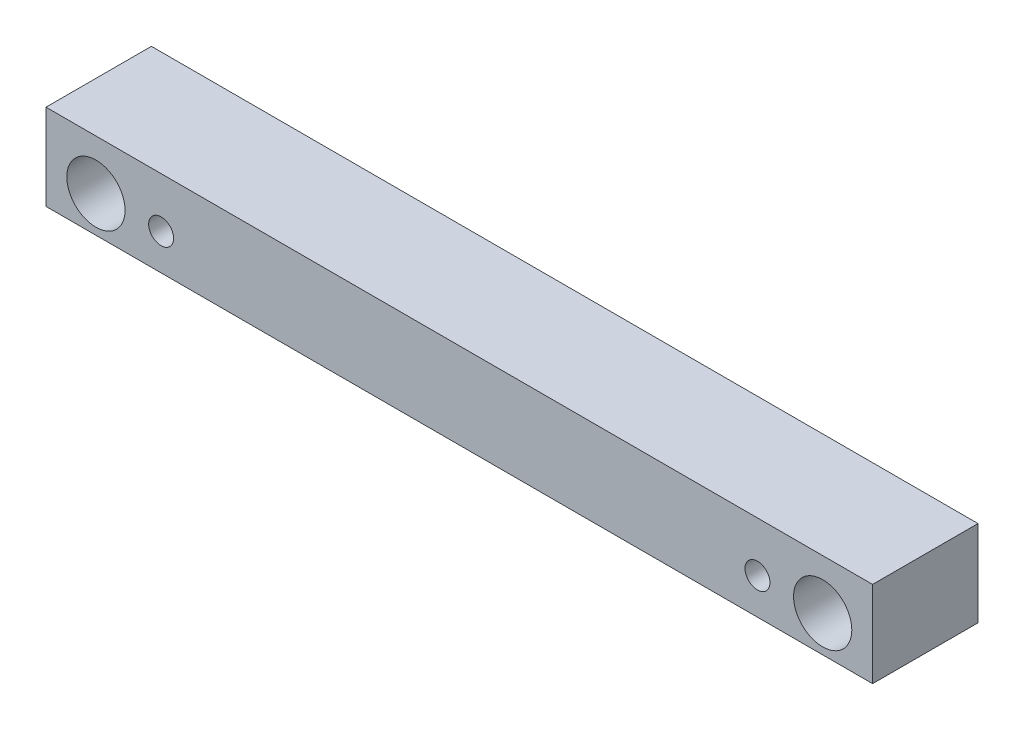
SolidWorks part; units mm, degrees
ref_plane "Płaszczyzna przednia" through (0, 0, 0) normal (0, 0, 1) x (1, 0, 0)
ref_plane "Płaszczyzna górna" through (0, 0, 0) normal (0, 1, 0) x (1, 0, 0)
ref_plane "Płaszczyzna prawa" through (0, 0, 0) normal (1, 0, 0) x (0, 0, -1)
sketch "Szkic1" plane through (0, 0, 0) normal (0, 0, 1) x (1, 0, 0)
  line L0 (-298, 198) -> (-298, 136)
  line L1 (-298, 136) -> (298, 136)
  line L2 (298, 136) -> (298, 198)
  line L3 (298, 198) -> (-298, 198)
extrude "Dodanie-wyciągnięcie1" add sketch "Szkic1" along normal blind 76
ref_plane "Płaszczyzna1" through (0, 0, 76) normal (0, 0, 1) x (1, 0, 0)
sketch "Szkic2" plane through (0, 0, 76) normal (0, 0, 1) x (1, 0, 0)
  circle A0 centre (262, 162) radius 21
extrude "Wytnij-wyciągnięcie1" cut sketch "Szkic2" against normal blind 76
sketch "Szkic3" plane through (0, 0, 76) normal (0, 0, 1) x (1, 0, 0)
  circle A0 centre (-262, 162) radius 21
extrude "Wytnij-wyciągnięcie2" cut sketch "Szkic3" against normal blind 76
ref_plane "Płaszczyzna2" through (215, 0, 0) normal (1, 0, 0) x (0, 0, -1)
sketch "Szkic4" plane through (215, 0, 0) normal (1, 0, 0) x (0, 0, -1)
  line L0 (-76, 162) -> (-76, 171)
  line L1 (-76, 171) -> (0, 171)
  line L2 (0, 171) -> (0, 162)
  line L3 (0, 162) -> (-76, 162)
  line L4 (0, 162) -> (-76, 162) construction
revolve "Wycięcie-obrót1" cut sketch "Szkic4" angle 360 about L4 reverse direction yes
ref_plane "Płaszczyzna3" through (-215, 0, 0) normal (1, 0, 0) x (0, 0, -1)
sketch "Szkic5" plane through (-215, 0, 0) normal (1, 0, 0) x (0, 0, -1)
  line L0 (-76, 162) -> (-76, 171)
  line L1 (-76, 171) -> (0, 171)
  line L2 (0, 171) -> (0, 162)
  line L3 (0, 162) -> (-76, 162)
  line L4 (0, 162) -> (-76, 162) construction
revolve "Wycięcie-obrót2" cut sketch "Szkic5" angle 360 about L4 reverse direction yes
ref_plane "IP1 XY" through (0, 0, 76) normal (0, 0, -1) x (-1, 0, 0)
ref_plane "IP1 XZ" through (0, 0, 0) normal (0, 1, 0) x (1, 0, 0)
ref_plane "IP1 YZ" through (0, 0, 0) normal (1, 0, 0) x (0, 0, -1)
ref_axis "IP1 X" through (-80.9, 0, 76) along (1, 0, 0)
ref_axis "IP1 Y" through (0, 50, 76) along (0, -1, 0)
ref_axis "IP1 Z" through (0, 0, -80.9) along (0, 0, 1)
sketch3d "IP1"
  point P0 (0, 0, 76)
ref_plane "IP2 XY" through (0, 0, 76) normal (0, 0, -1) x (-1, 0, 0)
ref_plane "IP2 XZ" through (0, 0, 0) normal (0, -1, 0) x (-1, 0, 0)
ref_plane "IP2 YZ" through (0, 0, 0) normal (-1, 0, 0) x (0, 0, 1)
ref_axis "IP2 X" through (80.9, 0, 76) along (-1, 0, 0)
ref_axis "IP2 Y" through (0, -50, 76) along (0, 1, 0)
ref_axis "IP2 Z" through (0, 0, -80.9) along (0, 0, 1)
sketch3d "IP2"
  point P0 (0, 0, 76)
